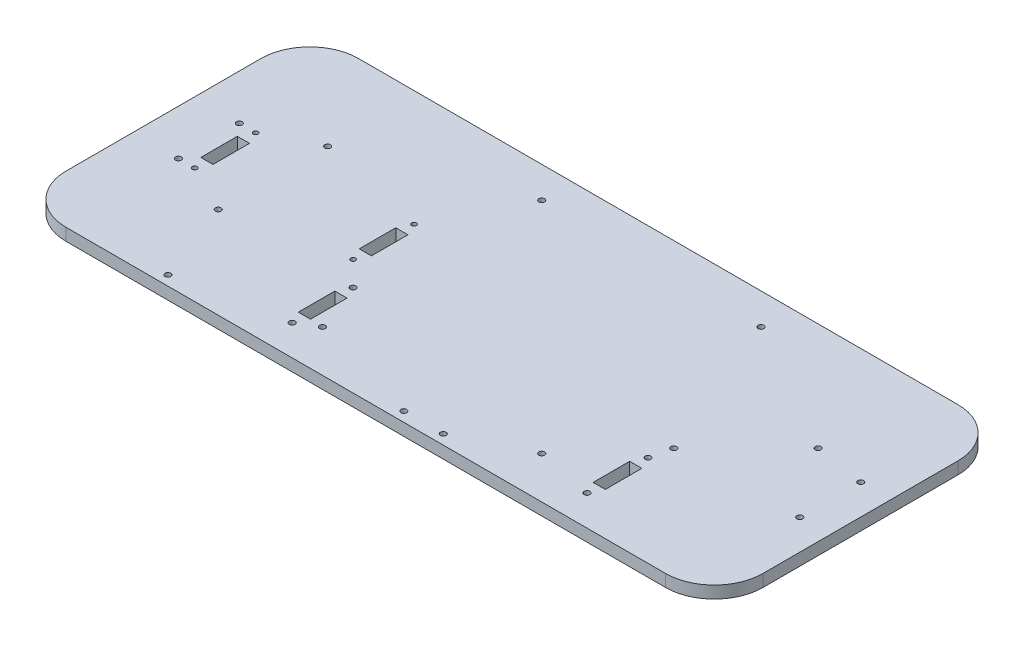
SolidWorks part; units mm, degrees
ref_plane "Front Plane" through (0, 0, 0) normal (0, 0, 1) x (1, 0, 0)
ref_plane "Top Plane" through (0, 0, 0) normal (0, 1, 0) x (1, 0, 0)
ref_plane "Right Plane" through (0, 0, 0) normal (1, 0, 0) x (0, 0, -1)
sketch "Sketch3" plane through (0, 0, 0) normal (0, 1, 0) x (1, 0, 0)
  line L1 (-156.21, -76.2) -> (156.21, -76.2)
  line L2 (-181.61, -50.8) -> (-181.61, 50.8)
  line L3 (-156.21, 76.2) -> (156.21, 76.2)
  line L4 (181.61, -50.8) -> (181.61, 50.8)
  line L5 (-181.61, -76.2) -> (181.61, 76.2) construction
  line L6 (-181.61, 76.2) -> (181.61, -76.2) construction
  arc A0 (156.21, -76.2) -> (181.61, -50.8) centre (156.21, -50.8) ccw
  arc A1 (156.21, 76.2) -> (181.61, 50.8) centre (156.21, 50.8) cw
  arc A2 (-156.21, -76.2) -> (-181.61, -50.8) centre (-156.21, -50.8) cw
  arc A3 (-181.61, 50.8) -> (-156.21, 76.2) centre (-156.21, 50.8) cw
  point P0 (0, 0)
  dimension "D3" = 25.4
  dimension "D1" = 152.4
  dimension "D2" = 363.22
extrude "Boss-Extrude2" add sketch "Sketch3" against normal blind 6.35
sketch "Sketch4" plane through (0, 0, 0) normal (0, 1, 0) x (1, 0, 0)
  line L0 (-181.61, 50.8) -> (-181.61, -50.8) construction
  line L1 (156.21, 76.2) -> (-156.21, 76.2) construction
  line L2 (181.61, -50.8) -> (181.61, 50.8) construction
  line L3 (139.446, 20.066) -> (101.854, 20.066) construction
  line L4 (139.446, 20.066) -> (139.446, -17.526) construction
  line L5 (139.446, -17.526) -> (101.854, -17.526) construction
  line L6 (101.854, 20.066) -> (101.854, -17.526) construction
  line L7 (139.446, 20.066) -> (101.854, -17.526) construction
  line L8 (139.446, -17.526) -> (101.854, 20.066) construction
  circle A0 centre (-44.45, 59.944) radius 1.5
  circle A1 centre (69.85, 59.944) radius 1.5
  circle A2 centre (69.85, -54.356) radius 1.5
  circle A3 centre (-44.45, -54.356) radius 1.5
  circle A4 centre (139.446, 20.066) radius 1.5
  circle A5 centre (101.854, -17.526) radius 1.5
  point P6 (120.65, 1.27)
  dimension "D3" = 3
  dimension "D10" = 3
  dimension "D11" = 3
  dimension "D1" = 137.16
  dimension "D2" = 16.256
  dimension "D6" = 42.164
  dimension "D7" = 56.134
  dimension "D8" = 37.592
  dimension "D9" = 37.592
  dimension "D4" = 2
  dimension "D5" = 2
extrude "Cut-Extrude1" cut sketch "Sketch4" against normal up to surface (6.35 mm away) up to face at (0, -6.35, 0)
sketch "Sketch5" plane through (0, 0, 0) normal (0, 1, 0) x (1, 0, 0)
  line L0 (181.61, 0) -> (-181.61, 0) construction
  line L1 (181.61, -50.8) -> (181.61, 50.8) construction
  line L2 (-181.61, 50.8) -> (-181.61, -50.8) construction
  line L3 (0, 76.2) -> (0, -76.2) construction
  line L4 (156.21, 76.2) -> (-156.21, 76.2) construction
  line L5 (-156.21, -76.2) -> (156.21, -76.2) construction
  line L6 (-108.204, 0) -> (-108.204, 16.7048) construction
  line L7 (-152.654, -9.525) -> (-146.304, -9.525)
  line L8 (-152.654, -9.525) -> (-152.654, 9.525)
  line L9 (-152.654, 9.525) -> (-146.304, 9.525)
  line L10 (-146.304, -9.525) -> (-146.304, 9.525)
  line L11 (-152.654, -9.525) -> (-146.304, 9.525) construction
  line L12 (-152.654, 9.525) -> (-146.304, -9.525) construction
  line L13 (-63.754, 9.525) -> (-70.104, -9.525) construction
  line L14 (-63.754, -9.525) -> (-70.104, 9.525) construction
  line L15 (-70.104, -9.525) -> (-70.104, 9.525)
  line L16 (-63.754, 9.525) -> (-70.104, 9.525)
  line L17 (-63.754, -9.525) -> (-63.754, 9.525)
  line L18 (-63.754, -9.525) -> (-70.104, -9.525)
  circle A0 centre (-149.479, 15.875) radius 1.25
  circle A1 centre (-149.479, -15.875) radius 1.25
  circle A2 centre (-66.929, -15.875) radius 1.25
  circle A3 centre (-66.929, 15.875) radius 1.25
  point P12 (-149.479, 0)
  point P17 (-149.479, 0)
  point P32 (-66.929, 0)
  dimension "D4" = 2.5
  dimension "D1" = 32.131
  dimension "D2" = 6.35
  dimension "D3" = 19.05
  dimension "D5" = 15.875
  dimension "D6" = 41.275
extrude "Cut-Extrude2" cut sketch "Sketch5" against normal up to surface (6.35 mm away) up to face at (-44.45, -6.35, 55.856)
sketch "Sketch6" plane through (0, 0, 0) normal (0, 1, 0) x (1, 0, 0)
  line L0 (-181.61, 0) -> (181.61, 0) construction
  line L1 (-181.61, 50.8) -> (-181.61, -50.8) construction
  line L2 (181.61, -50.8) -> (181.61, 50.8) construction
  line L3 (0, -76.2) -> (0, 76.2) construction
  line L4 (-156.21, -76.2) -> (156.21, -76.2) construction
  line L5 (156.21, 76.2) -> (-156.21, 76.2) construction
  line L6 (3.937, 0) -> (3.937, 19.6413) construction
  circle A0 centre (-157.988, 15.875) radius 1.5
  circle A1 centre (-157.988, -15.875) radius 1.5
  circle A2 centre (165.862, -15.875) radius 1.5
  circle A3 centre (165.862, 15.875) radius 1.5
  dimension "D2" = 3
  dimension "D1" = 23.622
  dimension "D3" = 15.875
  dimension "D4" = 161.925
extrude "Cut-Extrude3" cut sketch "Sketch6" against normal up to surface (6.35 mm away) up to face at (-66.929, -6.35, -14.625)
sketch "Sketch7" plane through (0, 0, 0) normal (0, 1, 0) x (1, 0, 0)
  line L0 (96.266, -53.975) -> (102.616, -34.925) construction
  line L1 (-63.754, -9.525) -> (-63.754, 9.525) construction
  line L2 (96.266, -34.925) -> (96.266, -53.975)
  line L3 (96.266, -53.975) -> (102.616, -53.975)
  line L4 (-57.404, -34.925) -> (-51.054, -34.925)
  line L5 (-57.404, -34.925) -> (-57.404, -53.975)
  line L6 (-57.404, -53.975) -> (-51.054, -53.975)
  line L7 (-51.054, -34.925) -> (-51.054, -53.975)
  line L8 (-57.404, -34.925) -> (-51.054, -53.975) construction
  line L9 (-57.404, -53.975) -> (-51.054, -34.925) construction
  line L10 (96.266, -34.925) -> (102.616, -34.925)
  line L11 (102.616, -34.925) -> (102.616, -53.975)
  line L12 (96.266, -34.925) -> (102.616, -53.975) construction
  line L13 (-156.21, -76.2) -> (156.21, -76.2) construction
  circle A0 centre (-54.229, -28.575) radius 1.5
  circle A1 centre (-54.229, -60.325) radius 1.5
  circle A2 centre (99.441, -60.325) radius 1.5
  circle A3 centre (99.441, -28.575) radius 1.5
  point P1 (99.441, -44.45)
  point P7 (-54.229, -44.45)
  dimension "D6" = 3
  dimension "D7" = 3
  dimension "D13" = 3
  dimension "D14" = 3
  dimension "D2" = 19.05
  dimension "D3" = 6.35
  dimension "D4" = 15.875
  dimension "D5" = 15.875
  dimension "D8" = 6.35
  dimension "D9" = 19.05
  dimension "D10" = 6.35
  dimension "D11" = 15.875
  dimension "D12" = 15.875
  dimension "D15" = 147.32
  dimension "D16" = 15.875
extrude "Cut-Extrude4" cut sketch "Sketch7" against normal up to surface (6.35 mm away) up to face at (165.862, -6.35, -14.375)
sketch "Sketch9" plane through (0, 0, 0) normal (0, 1, 0) x (1, 0, 0)
  line L0 (-146.304, 0) -> (-70.104, 0) construction
  line L1 (-146.304, -9.525) -> (-146.304, 9.525) construction
  line L2 (-70.104, 9.525) -> (-70.104, -9.525) construction
  line L3 (-108.204, 0) -> (-108.204, -76.2) construction
  line L4 (-156.21, -76.2) -> (156.21, -76.2) construction
  line L5 (-51.054, -53.975) -> (-51.054, -34.925) construction
  line L8 (31.242, -66.04) -> (31.242, -76.2) construction
  line L9 (10.668, -76.2) -> (18.796, -76.2) construction
  line L10 (10.668, -76.2) -> (10.668, -66.04) construction
  line L11 (10.668, -66.04) -> (18.796, -66.04) construction
  line L12 (18.796, -76.2) -> (18.796, -66.04) construction
  line L13 (10.668, -71.12) -> (18.796, -71.12) construction
  line L14 (31.242, -66.04) -> (39.37, -66.04) construction
  line L15 (39.37, -66.04) -> (39.37, -76.2) construction
  line L16 (39.37, -71.12) -> (35.306, -71.12) construction
  line L17 (35.306, -71.12) -> (31.242, -71.12) construction
  circle A0 centre (-108.204, -71.12) radius 1.5
  circle A1 centre (14.732, -71.12) radius 1.5
  circle A2 centre (35.306, -71.12) radius 1.5
  point P24 (14.732, -71.12)
  dimension "D1" = 3
  dimension "D3" = 3
  dimension "D2" = 5.08
  dimension "D4" = 5.08
  dimension "D5" = 61.722
  dimension "D6" = 69.85
  dimension "D7" = 12.446
extrude "Cut-Extrude6" cut sketch "Sketch9" against normal up to surface (6.35 mm away) up to face at (99.441, -6.35, 61.825)
sketch "Sketch10" plane through (0, 0, 0) normal (0, 1, 0) x (1, 0, 0)
  line L0 (-124.61, 28.5) -> (-124.61, -28.5) construction
  line L1 (-181.61, 0) -> (-124.61, 0) construction
  line L2 (-181.61, 50.8) -> (-181.61, -50.8) construction
  circle A0 centre (-124.61, 28.5) radius 1.5
  circle A1 centre (-124.61, -28.5) radius 1.5
  dimension "D1" = 3
  dimension "D2" = 57
  dimension "D3" = 57
extrude "Cut-Extrude7" cut sketch "Sketch10" against normal through all
